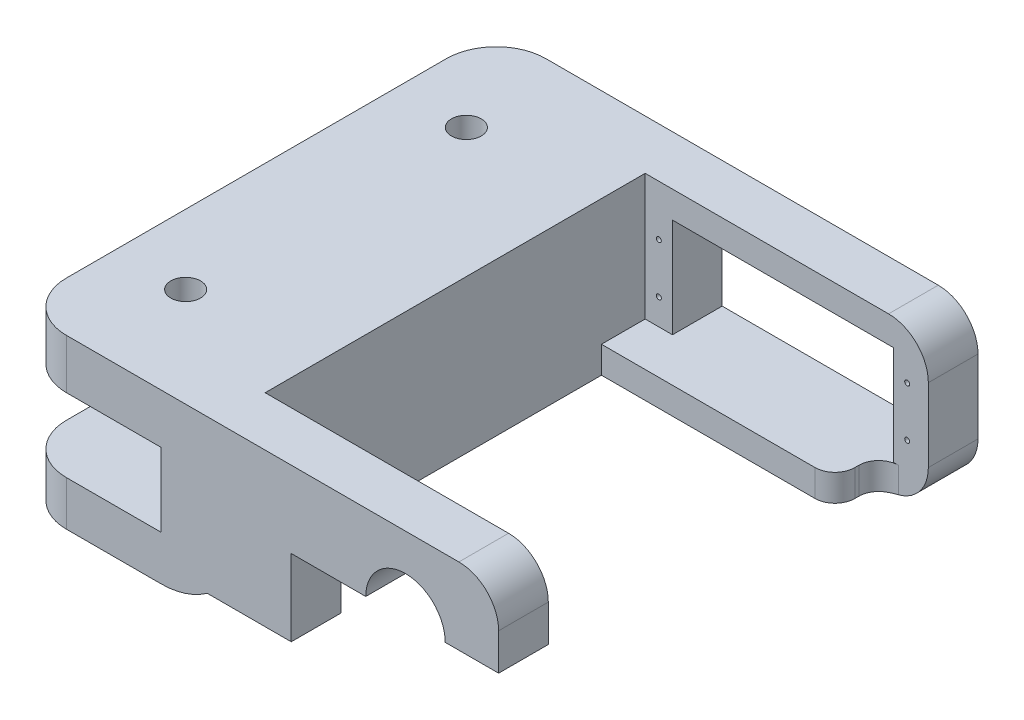
SolidWorks part; units mm, degrees
material "PLA 100% Infill"
ref_plane "Front Plane" through (0, 0, 0) normal (0, 0, 1) x (1, 0, 0)
ref_plane "Top Plane" through (0, 0, 0) normal (0, 1, 0) x (1, 0, 0)
ref_plane "Right Plane" through (0, 0, 0) normal (1, 0, 0) x (0, 0, -1)
sketch "Sketch1" plane through (0, 0, 0) normal (0, 0, 1) x (1, 0, 0)
  line L0 (0, 0) -> (97, 0)
  line L1 (97, -30.8) -> (0, -30.8)
  line L2 (0, -30.8) -> (0, -24.8)
  line L3 (0, -24.8) -> (29, -24.8)
  line L4 (29, -24.8) -> (29, -10)
  line L5 (29, -10) -> (0, -10)
  line L6 (0, -10) -> (0, 0)
  line L7 (97, 0) -> (97, -30.8)
  line L8 (26, -15.4) -> (97, -15.4) construction
  line L9 (0, -30.8) -> (0, -33.8)
  line L10 (0, -33.8) -> (29, -33.8)
  circle A1 centre (78.25, -15.4) radius 8
  arc A2 (29, -33.8) -> (38.3274, -30.8) centre (29, -17.8) ccw
  point P20 (97, -15.4)
  dimension "D1" = 16
  dimension "D9" = 16
  dimension "D2" = 14.8
  dimension "D3" = 10
  dimension "D4" = 18.75
  dimension "D5" = 29
  dimension "D6" = 97
  dimension "D7" = 6
  dimension "D8" = 29
  dimension "D10" = 3
extrude "Boss-Extrude1" add sketch "Sketch1" along normal blind 96.5 contours A1 L8 | L8 A1 | L10 A2 L1 L9 | L7 L1 L2 L3 L4 L5 L6 L0 region at (78.25, -18.7953, 0) region at (78.25, -12.0047, 0) region at (17.7396, -32.248, 0)
sketch "Sketch2" plane through (0, 0, 0) normal (0, 1, 0) x (1, 0, 0)
  line L0 (97, -96.5) -> (97, 0) construction
  line L1 (97, -10) -> (40, -10)
  line L2 (97, -10) -> (97, -86.5)
  line L3 (97, -86.5) -> (40, -86.5)
  line L4 (40, -10) -> (40, -86.5)
  line L5 (0, -96.5) -> (97, -96.5) construction
  dimension "D1" = 10
  dimension "D2" = 10
  dimension "D3" = 57
extrude "Cut-Extrude1" cut sketch "Sketch2" against normal blind 102
fillet "Fillet1" radius 8 4 edges at (97, 0, 5) (97, -30.8, 5) (97, -30.8, 91.5) (97, 0, 91.5)
sketch "Sketch3" plane through (0, 0, 0) normal (0, 1, 0) x (1, 0, 0)
  line L0 (14, 0) -> (14, -114.5) construction
  line L3 (0, -96.5) -> (0, 0) construction
  line L4 (0, -96.5) -> (89, -96.5) construction
  line L5 (0, 0) -> (89, 0) construction
  circle A0 centre (14, -20) radius 3
  circle A1 centre (14, -76.5) radius 3
  dimension "D4" = 6
  dimension "D1" = 14
  dimension "D2" = 20
  dimension "D3" = 20
extrude "Cut-Extrude2" cut sketch "Sketch3" against normal up to next
sketch "Sketch4" plane through (0, 0, 10) normal (0, 0, 1) x (1, 0, 0)
  line L0 (90, -5.4) -> (45.5, -5.4)
  line L1 (90, -25.4) -> (90, -5.4)
  line L2 (45.5, -25.4) -> (90, -25.4)
  line L3 (45.5, -25.4) -> (45.5, -5.4)
  line L4 (97, -15.4) -> (29, -15.4) construction
  line L5 (97, -22.8) -> (97, -8) construction
  line L7 (42.75, -10.1718) -> (42.75, -20.1718) construction
  line L8 (92.75, -10.1718) -> (92.75, -20.1718) construction
  line L9 (92.75, -20.1718) -> (29, -20.1718) construction
  circle A0 centre (92.75, -20.1718) radius 0.5
  circle A1 centre (92.75, -10.1718) radius 0.5
  circle A2 centre (42.75, -20.1718) radius 0.5
  circle A3 centre (42.75, -10.1718) radius 0.5
  point P1 (80.25, -15.4)
  point P21 (90, -15.4)
  dimension "D1" = 2.75
  dimension "D2" = 20
  dimension "D3" = 44.5
  dimension "D4" = 2.75
  dimension "D5" = 10
  dimension "D6" = 5.2282
  dimension "D7" = 9.75
  dimension "D8" = 7
  dimension "D9" = 10
extrude "Cut-Extrude3" cut sketch "Sketch4" against normal up to next
sketch "Sketch5" plane through (0, 0, 10) normal (0, 0, 1) x (1, 0, 0)
  line L0 (40, -30.8) -> (89, -30.8) construction
  line L2 (87, -25.4) -> (87, -30.8)
  line L3 (87, -30.8) -> (42.4962, -30.8)
  line L5 (45.5, -25.4) -> (90, -25.4) construction
  line L8 (42.4962, -30.8) -> (40, -30.8)
  line L9 (40, -25.4) -> (40, -30.8)
  line L10 (40, -25.4) -> (87, -25.4)
  line M11 (40, 0) -> (40, -30.8)
  line M12 (40, -30.8) -> (89, -30.8)
  arc M13 (89, -30.8) -> (97, -22.8) centre (89, -22.8) ccw
extrude "Boss-Extrude2" add sketch "Sketch5" along normal blind 8.8 contours L10 L2 M11 M12 M13 region at (63.5, -28.1, 10)
fillet "Fillet2" radius 4 2 edges at (87, -28.1, 18.8) (87, -28.1, 10)
sketch "Sketch6" plane through (0, 0, 96.5) normal (0, 0, 1) x (1, 0, 0)
  line L0 (86.25, -15.4) -> (97, -15.4)
  line L1 (97, -8) -> (97, -22.8) construction
  line L2 (70.25, -15.4) -> (55.25, -15.4)
  line L3 (55.25, -15.4) -> (55.25, -30.8)
  line L4 (89, -30.8) -> (38.3274, -30.8) construction
  line L5 (55.25, -30.8) -> (89, -30.8)
  line L6 (97, -22.8) -> (97, -15.4)
  circle A0 centre (78.25, -15.4) radius 8 construction
  arc A1 (89, -30.8) -> (97, -22.8) centre (89, -22.8) ccw
  arc A2 (70.25, -15.4) -> (86.25, -15.4) centre (78.25, -15.4) ccw
  dimension "D1" = 15
extrude "Cut-Extrude4" cut sketch "Sketch6" against normal blind 10
fillet "Fillet3" radius 10 4 edges at (0, -29.3, 0) (0, -5, 0) (0, -5, 96.5) (0, -29.3, 96.5)
ref_plane "Plane1" through (107, 0, 0) normal (1, 0, 0) x (0, 0, -1)
ref_plane "Plane2" through (0, 0, 106.5) normal (0, 0, 1) x (1, 0, 0)
